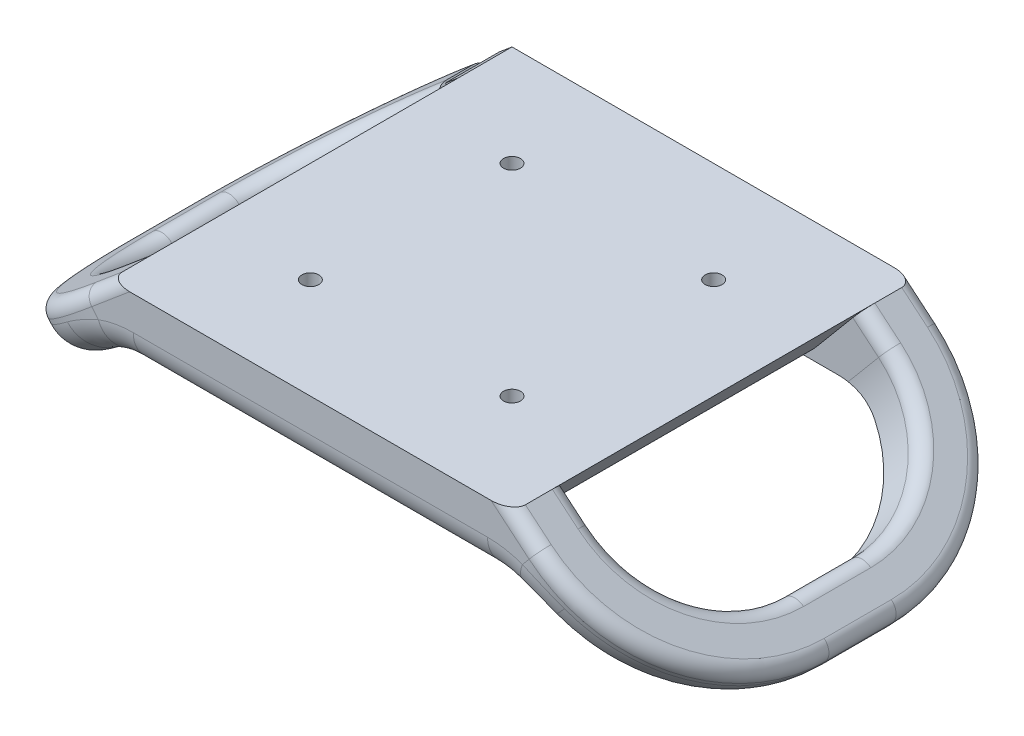
SolidWorks part; units mm, degrees
material "PET"
ref_plane "Front Plane" through (0, 0, 0) normal (0, 0, 1) x (1, 0, 0)
ref_plane "Top Plane" through (0, 0, 0) normal (0, 1, 0) x (1, 0, 0)
ref_plane "Right Plane" through (0, 0, 0) normal (1, 0, 0) x (0, 0, -1)
sketch "Sketch1" plane through (0, 0, 0) normal (0, 0, 1) x (1, 0, 0)
  line L0 (-19.05, 3.175) -> (-33.6431, -9.0701)
  line L1 (-19.05, -3.175) -> (19.05, -3.175)
  line L3 (-19.05, 3.175) -> (19.05, 3.175)
  line L5 (-19.05, -3.175) -> (19.05, 3.175) construction
  line L6 (-19.05, 3.175) -> (19.05, -3.175) construction
  line L7 (-33.6431, -9.0701) -> (-30.5164, -12.7964)
  line L8 (-30.5164, -12.7964) -> (-19.05, -3.175)
  line L9 (-19.05, 3.175) -> (-19.05, -3.175) construction
  line L10 (0, -1000) -> (0, 49000) construction
  line L11 (30.5164, -12.7964) -> (19.05, -3.175)
  line L12 (33.6431, -9.0701) -> (30.5164, -12.7964)
  line L13 (19.05, 3.175) -> (33.6431, -9.0701)
  point P0 (0, 0)
  dimension "D1" = 40
  dimension "D2" = 6.35
  dimension "D3" = 38.1
  dimension "D4" = 19.05
extrude "Main Body" add sketch "Sketch1" along normal blind 38.1
sketch "Sketch2" plane through (-9.4344, 11.2435, 0) normal (-0.6428, 0.766, 0) x (0.766, 0.6428, 0)
  line L0 (-26.5223, -22.225) -> (-26.5223, -15.875)
  line L1 (-15.7273, -5.08) -> (-12.5523, -5.08)
  line L2 (-31.6023, -38.1) -> (-31.6023, 0) construction
  line L3 (-12.5523, -33.02) -> (-15.7273, -33.02)
  line L4 (-1011.7033, -38.1) -> (48988.2967, -38.1) construction
  line L5 (-12.5523, -5.08) -> (-12.5523, -33.02)
  line L6 (-1012.5523, -19.05) -> (48987.4477, -19.05) construction
  line L7 (-12.5523, -38.1) -> (-12.5523, 0) construction
  line L8 (-31.6023, -15.875) -> (-31.6023, -22.225) construction
  line L9 (-15.7273, -15.875) -> (-15.7273, 0) construction
  line L10 (-12.5523, -1013.7143) -> (-12.5523, 48986.2857) construction
  line L11 (-15.7273, 0) -> (-12.5523, 0) construction
  line L12 (-15.7273, -38.1) -> (-12.5523, -38.1) construction
  line L13 (-15.7273, -38.1) -> (-31.6023, -38.1)
  line L14 (-31.6023, -38.1) -> (-31.6023, -22.225)
  line L15 (-15.7273, 0) -> (-31.6023, 0)
  line L16 (-31.6023, 0) -> (-31.6023, -15.875)
  arc A0 (-31.6023, -15.875) -> (-15.7273, 0) centre (-15.7273, -15.875) cw
  arc A1 (-31.6023, -22.225) -> (-15.7273, -38.1) centre (-15.7273, -22.225) ccw
  arc A2 (-26.5223, -15.875) -> (-15.7273, -5.08) centre (-15.7273, -15.875) cw
  arc A3 (-15.7273, -33.02) -> (-26.5223, -22.225) centre (-15.7273, -22.225) cw
  point P0 (-31.6023, -19.05)
  point P11 (-12.5523, -19.05)
  point P33 (-26.5223, -19.05)
  dimension "D1" = 3.175
  dimension "D2" = 5.08
  dimension "D3" = 5.08
  dimension "D4" = 3.175
  dimension "D5" = 5.08
extrude "Handle Cut 1" cut sketch "Sketch2" against normal through all
mirror "Handle Cut 2" about plane through (0, 0, 0) normal (1, 0, 0) of "Handle Cut 1"
sketch "Sketch4" plane through (-9.4344, 11.2435, 0) normal (-0.6428, 0.766, 0) x (0.766, 0.6428, 0)
  line L9 (-12.5523, -5.08) -> (-15.7273, -5.08) construction
  line L10 (-15.7273, 0) -> (-14.1398, 0)
  line L11 (-15.7273, 0) -> (-15.7273, -5.08)
  line L12 (-15.7273, -5.08) -> (-14.1398, -5.08)
  line L13 (-14.1398, 0) -> (-14.1398, -5.08)
extrude "Elastic Slot" cut sketch "Sketch4" against normal through all
sketch "Hole Locations" plane through (0, 3.175, 0) normal (0, 1, 0) x (1, 0, 0)
  line L0 (-1019.05, -19.05) -> (48980.95, -19.05) construction
  line L1 (-19.05, -33.02) -> (-19.05, -5.08) construction
  line L2 (0, -1000) -> (0, 49000) construction
  line L3 (19.05, 0) -> (-19.05, 0) construction
  line L5 (9.525, -28.575) -> (-9.525, -28.575)
  line L6 (9.525, -28.575) -> (9.525, -9.525)
  line L7 (9.525, -9.525) -> (-9.525, -9.525)
  line L8 (-9.525, -28.575) -> (-9.525, -9.525)
  line L9 (9.525, -28.575) -> (-9.525, -9.525) construction
  line L10 (9.525, -9.525) -> (-9.525, -28.575) construction
  point P5 (-19.05, -19.05)
  point P6 (0, -19.05)
  point P10 (0, 0)
  dimension "D1" = 19.05
  dimension "D2" = 19.05
hole_wizard "M2x0.4 Tapped Hole1" positions "Sketch6" profile "Sketch7" tap size "M2x0.4" standard "ANSI Metric" end condition through all
sketch "Sketch6" plane through (0, 3.175, 0) normal (0, 1, 0) x (1, 0, 0)
  point P0 (-9.525, -9.525)
  point P3 (9.525, -9.525)
  point P6 (9.525, -28.575)
  point P9 (-9.525, -28.575)
sketch "Sketch7" plane through (-9.525, 3.175, 9.525) normal (1, 0, 0) x (0, 0, 1)
  line L0 (0, 0) -> (0, 15.9714)
  line L1 (0, 15.9714) -> (0.8, 15.9714)
  line L2 (0.8, 15.9714) -> (0.8, 0)
  line L5 (0.8, 0) -> (0, 0)
  line L11 (0, -6.35) -> (0, 107.95) construction
  dimension "Thru Tap Drill Dia." = 1.6
  dimension "Thru Tap Drill Depth" = 15.9714
cosmetic thread "Hole Thread1" parameters "D2"=2
cosmetic thread "Hole Thread2" parameters "D2"=2
cosmetic thread "Hole Thread3" parameters "D2"=2
cosmetic thread "Hole Thread4" parameters "D2"=2
fillet "Fillet1" radius 6.35 4 edges at (19.05, -3.175, 35.528) (19.05, -3.175, 2.572) (-19.05, -3.175, 2.572) (-19.05, -3.175, 35.528)
fillet "Fillet2" radius 3.175 2 edges at (13.7217, -3.175, 19.05) (-13.7217, -3.175, 19.05)
fillet "Outside Rounding" radius 3.175 15 edges at (30.5164, -12.7964, 19.05) (27.7859, -10.5053, 32.2483) (19.6985, -3.9069, 37.989) (17.2675, -3.197, 38.1) (0, -3.175, 38.1) (-17.2675, -3.197, 38.1) (-19.1095, -3.6342, 38.0509) (-27.7859, -10.5053, 32.2483) (-30.5164, -12.7964, 19.05) (-27.7353, -10.4629, 5.7713) (-19.7434, -3.8865, 0.1135) (0.4724, -3.175, 0) (17.2675, -3.197, 0) (19.1095, -3.6342, 0.0491) (27.7859, -10.5053, 5.8517)
fillet "Topside Rounding" radius 1.27 18 edges at (-27.3296, -3.7724, 8.2418) (-20.2661, 2.1546, 33.02) (-27.3296, -3.7724, 29.8582) (-20.2661, 2.1546, 38.1) (-30.0813, -6.0813, 33.4503) (-30.0813, -6.0813, 4.6497) (20.2661, 2.1546, 38.1) (30.0813, -6.0813, 33.4503) (33.6431, -9.0701, 19.05) (20.2661, 2.1546, 0) (20.2661, 2.1546, 5.08) (27.3296, -3.7724, 8.2418) (29.7516, -5.8047, 19.05) (20.2661, 2.1546, 33.02) (-29.7516, -5.8047, 19.05) (-33.6431, -9.0701, 19.05) (30.0813, -6.0813, 4.6497) (27.3296, -3.7724, 29.8582)
equation "\"D3@Sketch2\"=\"D2@Sketch2\""
equation "\"D4@Sketch2\"=\"D1@Sketch2\""
equation "\"D5@Sketch2\"=\"D3@Sketch2\""
